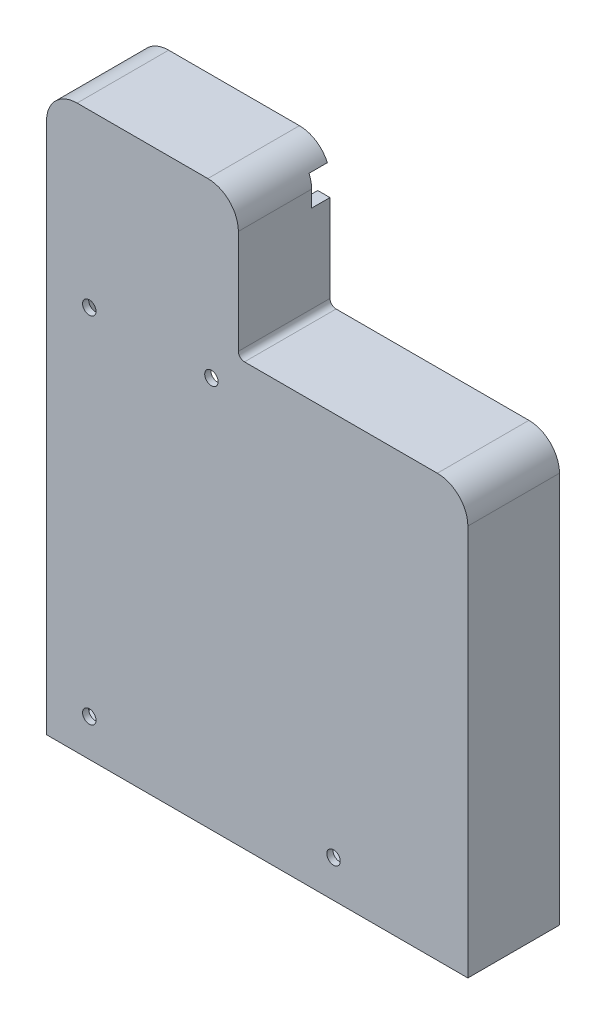
SolidWorks part; units mm, degrees
other "Markup1"
sketch "Sketch13" plane through (0.4487, 1125.5894, 1303.4729) normal (-0.633, 0.4523, -0.6282) x (-0.2198, -0.8831, -0.4145)
ref_plane "Front Plane" through (0, 0, 0) normal (0, 0, 1) x (1, 0, 0)
ref_plane "Top Plane" through (0, 0, 0) normal (0, 1, 0) x (1, 0, 0)
ref_plane "Right Plane" through (0, 0, 0) normal (1, 0, 0) x (0, 0, -1)
sketch "Sketch3" plane through (0, 0, 1303.4729) normal (0, 0, 1) x (1, 0, 0)
  line L0 (787.6501, 933.5894) -> (787.6501, 1120.5894) construction
  line L1 (787.6501, 1035.4965) -> (787.6501, 1120.5894)
  line L2 (839.6501, 1033.4965) -> (854.6497, 1033.4965)
  line L3 (818.0661, 1100.5894) -> (834.6501, 1100.5894) construction
  line L4 (815.0661, 1120.5894) -> (815.0661, 1103.5894) construction
  line L5 (790.6501, 1123.5894) -> (812.0661, 1123.5894) construction
  line L6 (852.6501, 1097.5883) -> (852.6501, 1035.4965)
  line L7 (818.0661, 1100.5894) -> (834.6501, 1100.5894)
  line L8 (815.0661, 1120.5894) -> (815.0661, 1103.5894)
  line L9 (790.6501, 1123.5894) -> (812.0661, 1123.5894)
  line L10 (787.6501, 1035.4965) -> (837.6501, 1035.4965) construction
  line L11 (787.6501, 1035.4965) -> (837.6501, 1035.4965)
  line L12 (854.6497, 1097.5883) -> (854.6497, 1033.4965)
  line L13 (785.6501, 1033.4965) -> (839.6501, 1033.4965)
  line L14 (785.6501, 1033.4965) -> (785.6501, 1120.5898)
  line L15 (790.6497, 1125.5894) -> (812.0665, 1125.5894)
  line L16 (817.0661, 1120.5898) -> (817.0661, 1103.5898)
  line L17 (818.0665, 1102.5894) -> (834.6505, 1102.5894)
  line L18 (834.6501, 1100.5894) -> (849.6501, 1100.5894)
  line L19 (834.6505, 1102.5894) -> (849.6501, 1102.5894)
  line L20 (839.6501, 1097.5883) -> (839.6501, 1033.4965) construction
  line L21 (837.6501, 1097.5883) -> (837.6501, 1035.4965) construction
  line L22 (852.6501, 1035.4965) -> (837.6501, 1035.4965)
  arc A1 (815.0661, 1103.5894) -> (818.0661, 1100.5894) centre (818.0672, 1103.5905) ccw construction
  arc A2 (815.0661, 1120.5894) -> (812.0661, 1123.5894) centre (812.065, 1120.5883) ccw construction
  arc A3 (790.6501, 1123.5894) -> (787.6501, 1120.5894) centre (790.6512, 1120.5883) ccw construction
  arc A5 (815.0661, 1103.5894) -> (818.0661, 1100.5894) centre (818.0672, 1103.5905) ccw
  arc A6 (815.0661, 1120.5894) -> (812.0661, 1123.5894) centre (812.065, 1120.5883) ccw
  arc A7 (790.6501, 1123.5894) -> (787.6501, 1120.5894) centre (790.6512, 1120.5883) ccw
  arc A8 (790.6497, 1125.5894) -> (785.6501, 1120.5898) centre (790.6512, 1120.5883) ccw
  arc A9 (817.0661, 1120.5898) -> (812.0665, 1125.5894) centre (812.065, 1120.5883) ccw
  arc A10 (817.0661, 1103.5898) -> (818.0665, 1102.5894) centre (818.0672, 1103.5905) ccw
  arc A11 (854.6497, 1097.5883) -> (849.6501, 1102.5894) centre (849.6486, 1097.5883) ccw
  arc A12 (852.6501, 1097.5883) -> (849.6501, 1100.5894) centre (849.649, 1097.5883) ccw
  arc A13 (839.6501, 1097.5883) -> (834.6505, 1102.5894) centre (834.649, 1097.5883) ccw construction
  arc A14 (837.6501, 1097.5883) -> (834.6501, 1100.5894) centre (834.649, 1097.5883) ccw construction
  point P3 (0, 0)
  dimension "D1" = 2
sketch "Sketch6" plane through (0, 0, 1303.4729) normal (0, 0, 1) x (1, 0, 0)
  line L0 (787.6501, 1035.4965) -> (837.6501, 1035.4965) construction
  line L2 (818.0661, 1100.5894) -> (834.6501, 1100.5894) construction
  line L3 (815.0661, 1120.5894) -> (815.0661, 1103.5894) construction
  line L4 (790.6501, 1123.5894) -> (812.0661, 1123.5894) construction
  line L5 (787.6501, 1035.4965) -> (787.6501, 1120.5894) construction
  line L6 (787.6501, 1035.4965) -> (837.6501, 1035.4965)
  line L8 (818.0661, 1100.5894) -> (834.6501, 1100.5894)
  line L9 (815.0661, 1120.5894) -> (815.0661, 1103.5894)
  line L10 (790.6501, 1123.5894) -> (812.0661, 1123.5894)
  line L11 (787.6501, 1035.4965) -> (787.6501, 1120.5894)
  line L12 (852.6501, 1035.4965) -> (837.6501, 1035.4965) construction
  line L13 (852.6501, 1097.5883) -> (852.6501, 1035.4965) construction
  line L14 (834.6501, 1100.5894) -> (849.6501, 1100.5894) construction
  line L15 (852.6501, 1035.4965) -> (837.6501, 1035.4965)
  line L16 (852.6501, 1097.5883) -> (852.6501, 1035.4965)
  line L17 (834.6501, 1100.5894) -> (849.6501, 1100.5894)
  arc A1 (815.0661, 1103.5894) -> (818.0661, 1100.5894) centre (818.0672, 1103.5905) ccw construction
  arc A2 (815.0661, 1120.5894) -> (812.0661, 1123.5894) centre (812.065, 1120.5883) ccw construction
  arc A3 (790.6501, 1123.5894) -> (787.6501, 1120.5894) centre (790.6512, 1120.5883) ccw construction
  arc A5 (815.0661, 1103.5894) -> (818.0661, 1100.5894) centre (818.0672, 1103.5905) ccw
  arc A6 (815.0661, 1120.5894) -> (812.0661, 1123.5894) centre (812.065, 1120.5883) ccw
  arc A7 (790.6501, 1123.5894) -> (787.6501, 1120.5894) centre (790.6512, 1120.5883) ccw
  arc A8 (852.6501, 1097.5883) -> (849.6501, 1100.5894) centre (849.649, 1097.5883) ccw construction
  arc A9 (852.6501, 1097.5883) -> (849.6501, 1100.5894) centre (849.649, 1097.5883) ccw
extrude "Boss-Extrude1" add sketch "Sketch3" along normal blind 15
extrude "Boss-Extrude2" add sketch "Sketch6" along normal blind 15
extrude "Cut-Extrude1" cut sketch "Sketch6<2>" along normal blind 14
sketch "Sketch6<2>" plane through (0, 0, 1303.4729) normal (0, 0, 1) x (1, 0, 0) same geometry as "Sketch6"
sketch "Sketch8" plane through (0, 0, 1303.4729) normal (0, 0, 1) x (1, 0, 0)
  line L10 (791.5267, 1122.6166) -> (784.8275, 1122.6166)
  line L11 (791.5267, 1122.6166) -> (791.5267, 1117.8952)
  line L12 (791.5267, 1117.8952) -> (784.8275, 1117.8952)
  line L13 (784.8275, 1122.6166) -> (784.8275, 1117.8952)
  line L14 (809.8444, 1122.6166) -> (818.0733, 1122.6166)
  line L15 (809.8444, 1122.6166) -> (809.8444, 1117.8952)
  line L16 (809.8444, 1117.8952) -> (818.0733, 1117.8952)
  line L17 (818.0733, 1122.6166) -> (818.0733, 1117.8952)
extrude "Cut-Extrude7" cut sketch "Sketch8" along normal blind 3
sketch "Sketch10" plane through (0, 0, 1303.4729) normal (0, 0, 1) x (1, 0, 0)
  circle A0 centre (832.6501, 1039.5894) radius 1.1 construction
  circle A1 centre (792.6501, 1039.5894) radius 1.1 construction
  circle A2 centre (792.6501, 1097.5894) radius 1.1 construction
  circle A3 centre (812.6501, 1097.5894) radius 1.1 construction
  circle A4 centre (832.6501, 1039.5894) radius 1.1
  circle A5 centre (792.6501, 1039.5894) radius 1.1
  circle A6 centre (792.6501, 1097.5894) radius 1.1
  circle A7 centre (812.6501, 1097.5894) radius 1.1
  point P12 (0, 0)
extrude "Cut-Extrude9" cut sketch "Sketch10" along normal up to surface (15 mm away) up to face at (818.5993, 1096.8607, 1318.4729)
